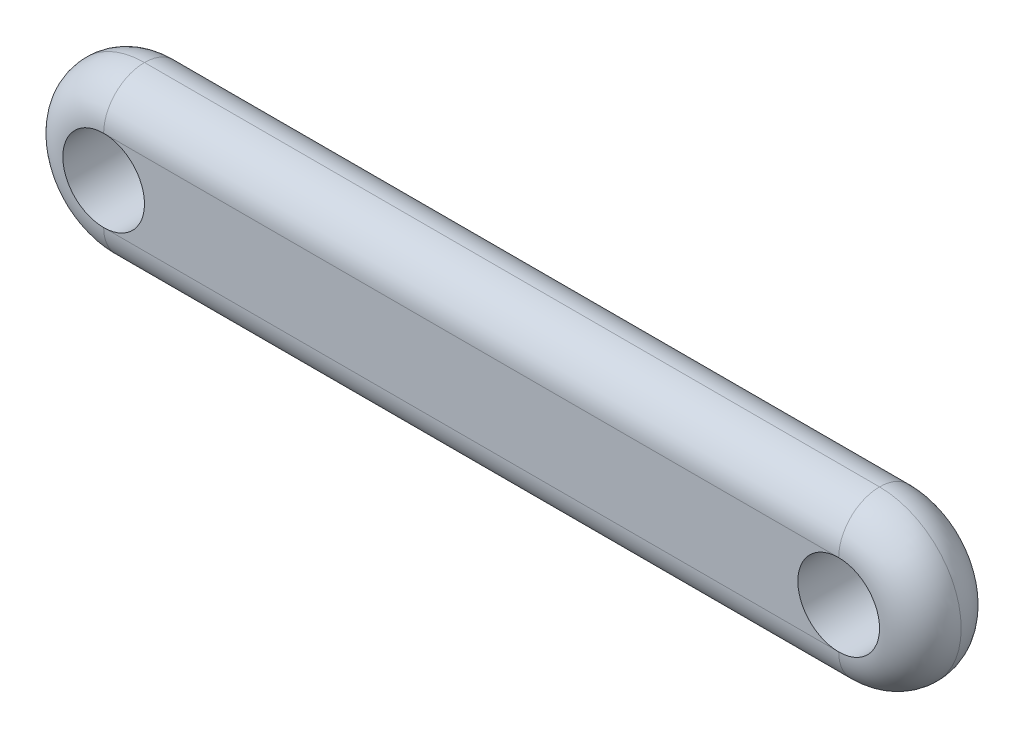
SolidWorks part; units mm, degrees
ref_plane "Front Plane" through (0, 0, 0) normal (0, 0, 1) x (1, 0, 0)
ref_plane "Top Plane" through (0, 0, 0) normal (0, 1, 0) x (1, 0, 0)
ref_plane "Right Plane" through (0, 0, 0) normal (1, 0, 0) x (0, 0, -1)
sketch "Sketch2" plane through (0, 0, 0) normal (0, 0, 1) x (1, 0, 0)
  line L0 (0, 0) -> (0, -4.8819) construction
  line L1 (0, 0) -> (-22.5, 0) construction
  line L2 (-22.5, 5) -> (22.5, 5)
  line L3 (-22.5, -5) -> (22.5, -5)
  arc A0 (-22.5, 5) -> (-22.5, -5) centre (-22.5, 0) ccw
  circle A1 centre (-22.5, 0) radius 2.5
  circle A2 centre (22.5, 0) radius 2.5
  arc A3 (22.5, 5) -> (22.5, -5) centre (22.5, 0) cw
  point P10 (0, 5)
  point P11 (0, -5)
  dimension "D1" = 10
  dimension "D3" = 5
  dimension "D4" = 45
extrude "Boss-Extrude1" add sketch "Sketch2" along normal blind 5
fillet "Fillet1" radius 2.5 8 edges at (0, -5, 5) (0, -5, 0) (27.5, 0, 5) (27.5, 0, 0) (-27.5, 0, 5) (-27.5, 0, 0) (0, 5, 5) (0, 5, 0)
